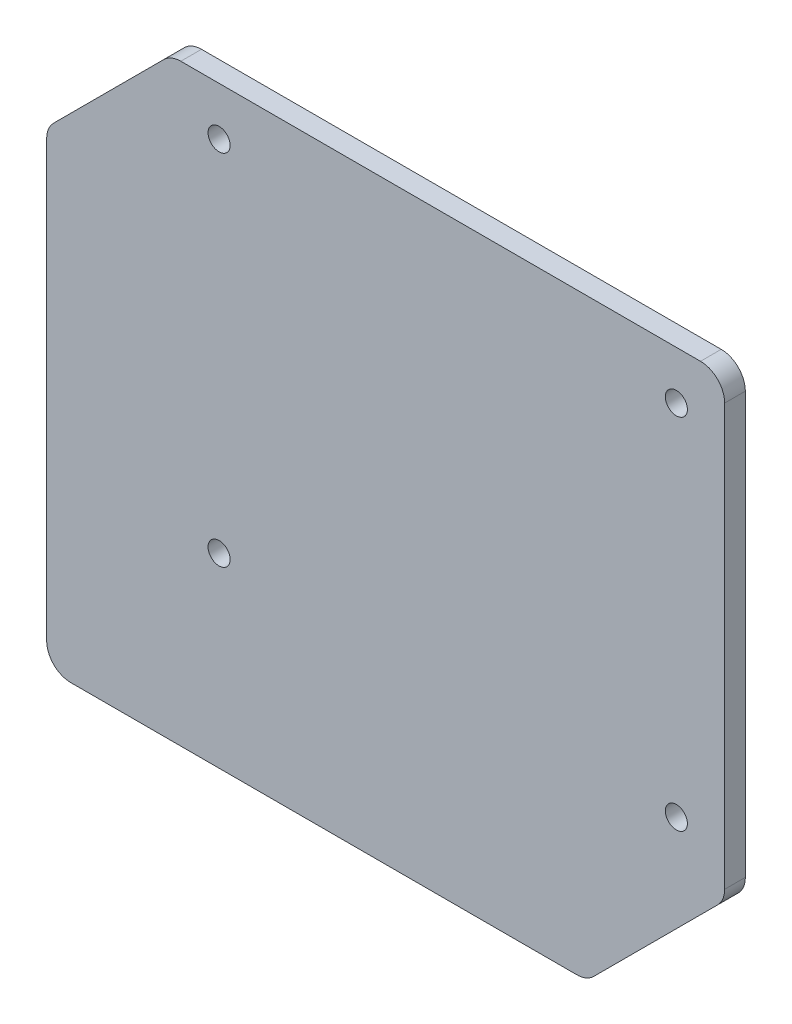
SolidWorks part; units mm, degrees
material "Acrylic (Medium-high impact)"
ref_plane "Front Plane" through (0, 0, 0) normal (0, 0, 1) x (1, 0, 0)
ref_plane "Top Plane" through (0, 0, 0) normal (0, 1, 0) x (1, 0, 0)
ref_plane "Right Plane" through (0, 0, 0) normal (1, 0, 0) x (0, 0, -1)
sketch "Sketch1" plane through (0, 0, 0) normal (0, 0, 1) x (1, 0, 0)
  line L0 (0, 66) -> (-18, 48)
  line L1 (0, 0) -> (80.3, 0)
  line L2 (0, 0) -> (0, 66)
  line L3 (0, 66) -> (80.3, 66)
  line L4 (80.3, 0) -> (80.3, 66)
  line L5 (-18, 48) -> (-18, -20)
  line L6 (-18, -20) -> (60.3, -20)
  line L7 (60.3, -20) -> (80.3, 0)
  dimension "D1" = 80.3
  dimension "D2" = 66
  dimension "D3" = 20
  dimension "D4" = 18
  dimension "D5" = 45
  dimension "D6" = 45
extrude "Boss-Extrude1" add sketch "Sketch1" along normal blind 3 contours L6 L7 L1 L2 L0 L5 | L1 L4 L3 L2 region at (-1.3061, 33, 0) region at (40.15, 33, 0)
fillet "Fillet1" radius 3.5 6 edges at (80.3, 0, 1.5) (60.3, -20, 1.5) (-18, -20, 1.5) (-18, 48, 1.5) (80.3, 66, 1.5) (0, 66, 1.5)
hole_wizard "Ø3.2 (3.2) Diameter Hole1" positions "Sketch5" profile "Sketch6" hole size "Ø3.2" standard "ANSI Metric" end condition through all
sketch "Sketch5" plane through (0, 0, 3) normal (0, 0, 1) x (1, 0, 0)
  line L5 (80.3, 1.4497) -> (80.3, 62.5) construction
  line L7 (1.4497, 66) -> (76.8, 66) construction
  point P0 (7, 59)
  point P2 (73.3, 59)
  point P4 (73.3, 7)
  point P6 (7, 7)
  dimension "D1" = 7
  dimension "D2" = 7
  dimension "D3" = 66.3
  dimension "D4" = 52
sketch "Sketch6" plane through (7, 59, 3) normal (1, 0, 0) x (0, -1, 0)
  line L0 (0, 0) -> (0, 3)
  line L1 (0, 3) -> (1.6, 3)
  line L2 (1.6, 3) -> (1.6, 0)
  line L5 (1.6, 0) -> (0, 0)
  line L11 (0, -6.35) -> (0, 107.95) construction
  dimension "Thru Hole Dia." = 3.2
  dimension "Thru Hole Depth" = 3
